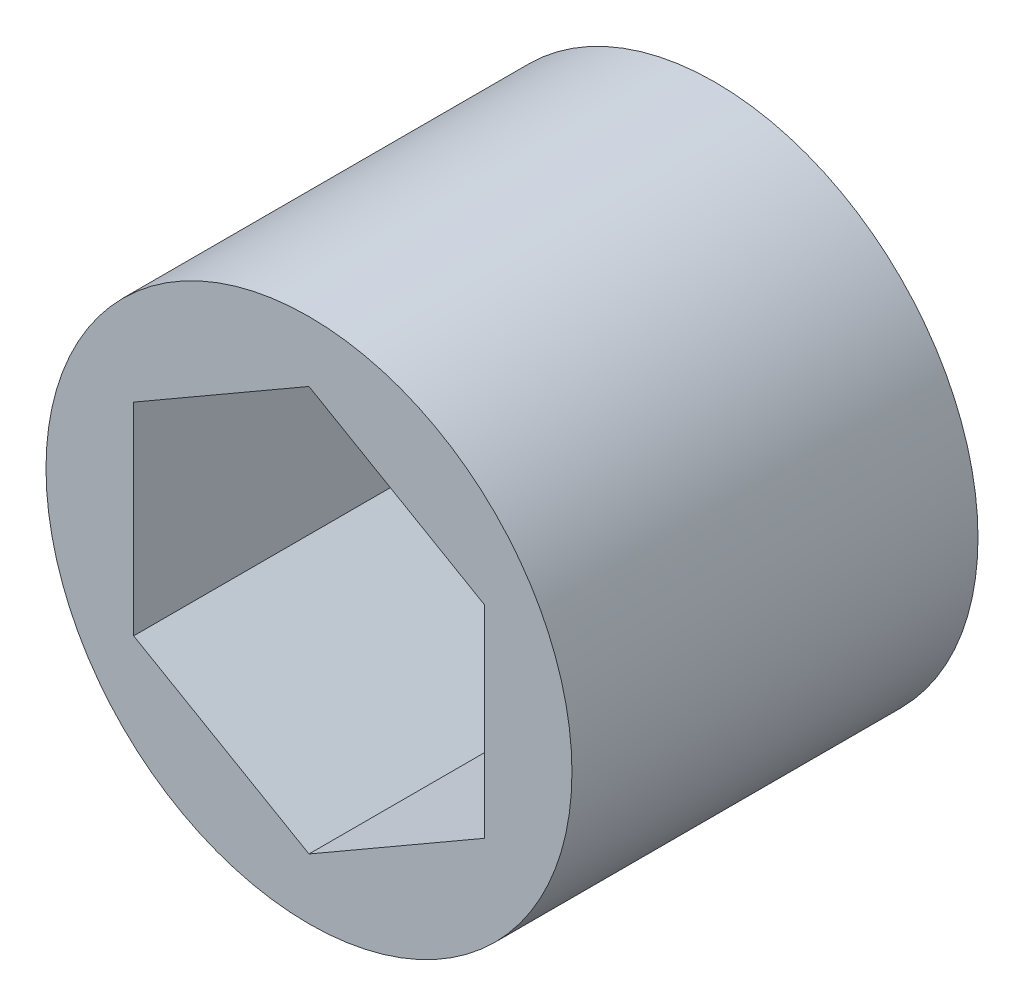
SolidWorks part; units mm, degrees
ref_plane "Front Plane" through (0, 0, 0) normal (0, 0, 1) x (1, 0, 0)
ref_plane "Top Plane" through (0, 0, 0) normal (0, 1, 0) x (1, 0, 0)
ref_plane "Right Plane" through (0, 0, 0) normal (1, 0, 0) x (0, 0, -1)
sketch "Sketch1" plane through (0, 0, 0) normal (0, 0, 1) x (1, 0, 0)
  line L1 (0, 7.3323) -> (-6.35, 3.6662)
  line L2 (-6.35, 3.6662) -> (-6.35, -3.6662)
  line L3 (-6.35, -3.6662) -> (0, -7.3323)
  line L4 (0, -7.3323) -> (6.35, -3.6662)
  line L5 (6.35, -3.6662) -> (6.35, 3.6662)
  line L6 (6.35, 3.6662) -> (0, 7.3323)
  circle A0 centre (0, 0) radius 6.35 construction
  circle A1 centre (0, 0) radius 9.525
  point P10 (0, 0)
  dimension "D1" = 19.05
  dimension "D2" = 12.7
extrude "Boss-Extrude1" add sketch "Sketch1" along normal mid plane 14.7066
